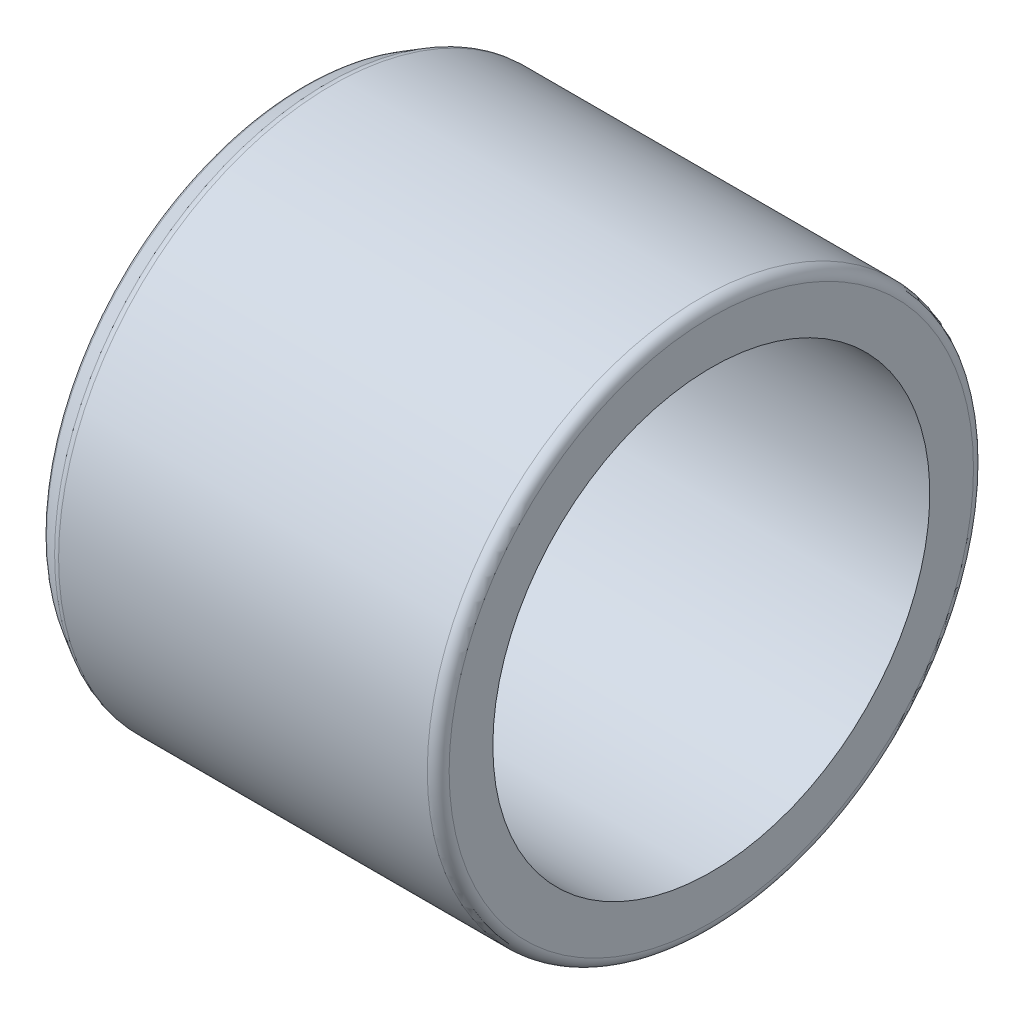
SolidWorks part; units mm, degrees
material "PE Высокой плотности"
ref_plane "Спереди" through (0, 0, 0) normal (0, 0, 1) x (1, 0, 0)
ref_plane "Сверху" through (0, 0, 0) normal (0, 1, 0) x (1, 0, 0)
ref_plane "Справа" through (0, 0, 0) normal (1, 0, 0) x (0, 0, -1)
sketch "Эскиз1" plane through (0, 0, 0) normal (0, 0, 1) x (1, 0, 0)
  line L0 (-18.75, 0) -> (18.75, 0) construction
  line L1 (-18.75, 0) -> (-18.75, 25) construction
  line L2 (-18.75, 25) -> (18.75, 25) construction
  line L3 (18.75, 25) -> (18.75, 0) construction
  line L4 (-18.75, 25) -> (18.75, 25) construction
  line L5 (-18.75, 18.1) -> (18.75, 18.1) construction
  line L6 (-18.75, 20) -> (18.75, 20) construction
  line L7 (18.75, 20) -> (18.75, 24)
  line L8 (17.75, 25) -> (-16, 25)
  line L9 (-16.5, 24.866) -> (-18.25, 23.8557)
  line L10 (-18.75, 22.9896) -> (-18.75, 19.1)
  line L11 (-17.75, 18.1) -> (-16, 18.1)
  line L12 (-16, 18.1) -> (-16, 20)
  line L13 (-16, 20) -> (18.75, 20)
  line L14 (-16, 18.1) -> (-16, 15.4706) construction
  arc A0 (-18.75, 19.1) -> (-17.75, 18.1) centre (-17.75, 19.1) ccw
  arc A1 (-18.25, 23.8557) -> (-18.75, 22.9896) centre (-17.75, 22.9896) ccw
  arc A2 (-16, 25) -> (-16.5, 24.866) centre (-16, 24) ccw
  arc A3 (18.75, 24) -> (17.75, 25) centre (17.75, 24) ccw
  point P11 (0, 25)
  point P12 (0, 25)
  point P13 (0, 20)
  point P14 (0, 18.1)
  point P27 (-16.2679, 25)
  point P31 (-16, 0)
  dimension "D4" = 37.5
  dimension "D3" = 1
  dimension "D1н/2" = 25
  dimension "D1в/2" = 25
  dimension "D2н/2" = 20
  dimension "D2в/2" = 18.1
  dimension "Dст" = 5
  dimension "D6" = 33.75
  dimension "D7" = 30
revolve "Повернуть1" add sketch "Эскиз1" angle 360 about L0
other "Точка соединения1" parameters "Диаметр"=40, "StubLength"=0
ref_axis "Ось2" through (-6, 0, 0) along (-1, 0, 0)
other "Точка маршрута1"
sketch "Эскиз2" plane through (0, 0, 0) normal (0, 0, 1) x (1, 0, 0)
  point P1 (18.75, 18.1)
equation "\"D3@Эскиз1\" = \"St\" / 5"
equation "\"St\"= \"D1в/2@Эскиз1\" - \"D2н/2@Эскиз1\""
equation "\"D6@Эскиз1\" = \"D4@Эскиз1\" * 0.9"
equation "\"D4@Эскиз1\" = 1.5 * \"D1н/2@Эскиз1\""
